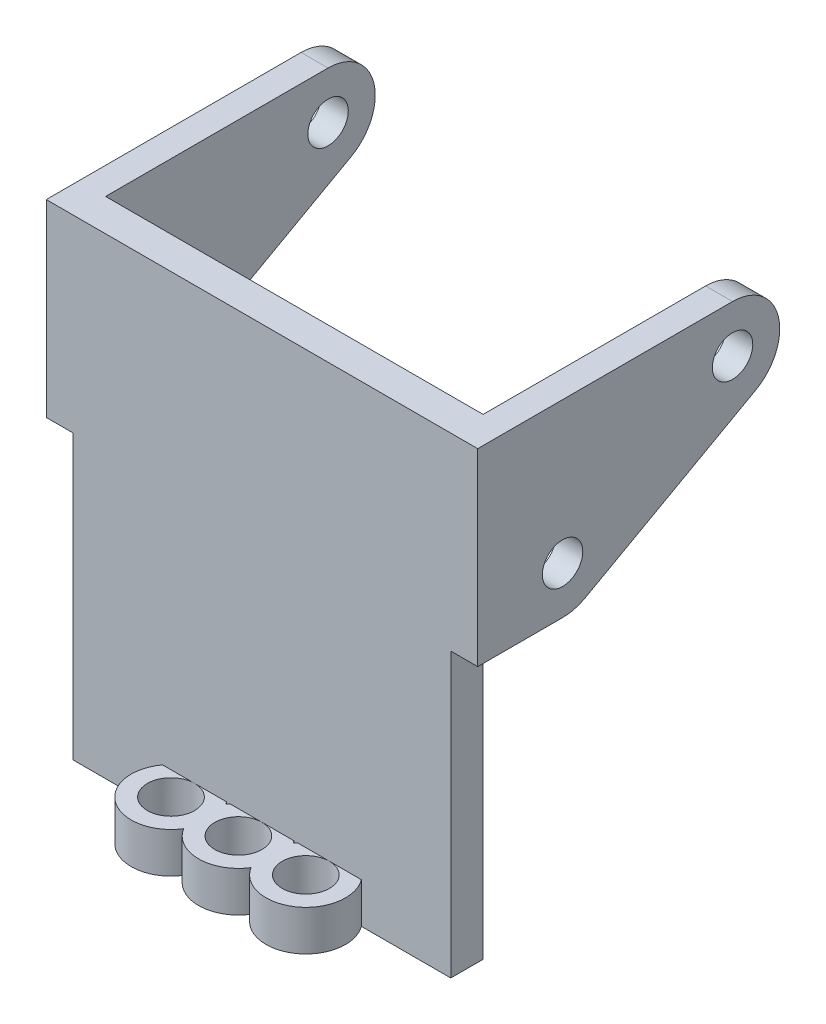
SolidWorks part; units mm, degrees
note: The reader was unsure of these and kept them because the rebuilt part matched: shared geometry of "Sketch4<2>".
ref_plane "Front Plane" through (0, 0, 0) normal (0, 0, 1) x (1, 0, 0)
ref_plane "Top Plane" through (0, 0, 0) normal (0, 1, 0) x (1, 0, 0)
ref_plane "Right Plane" through (0, 0, 0) normal (1, 0, 0) x (0, 0, -1)
sketch "Sketch2" plane through (0, 0, 0) normal (0, 1, 0) x (1, 0, 0)
  line L0 (-5, 0) -> (5, 0) construction
  circle A0 centre (0, 0) radius 1.75
  circle A1 centre (5, 0) radius 1.75
  circle A2 centre (-5, 0) radius 1.75
  dimension "D1" = 3.5
  dimension "D2" = 5
extrude "Extrude-Thin1" add sketch "Sketch2" along normal blind 3 thin contours A2 | A0 | A1
sketch "Sketch3" plane through (0, 0, 0) normal (1, 0, 0) x (0, 0, -1)
  line L0 (1.75, 0) -> (1.75, 35)
  line L1 (-2.95, 0) -> (2.95, 0) construction
  line L2 (4.15, 35) -> (54.15, 35) construction
extrude "Extrude-Thin2" add sketch "Sketch3" along normal up to surface (14 mm away) and the other way up to surface (14 mm away) thin
sketch "Sketch4" plane through (14, 0, 0) normal (1, 0, 0) x (0, 0, -1)
  line L0 (20.65, 35) -> (1.75, 35)
  line L1 (1.75, 35) -> (1.75, 21)
  line L2 (1.75, 0) -> (1.75, 35) construction
  line L3 (1.75, 21) -> (8.0415, 21)
  line L4 (9.7404, 21.44) -> (22.3489, 28.44)
  circle A0 centre (20.65, 31.5) radius 1.5 construction
  circle A1 centre (8.0415, 24.5) radius 1.5 construction
  circle A2 centre (20.65, 31.5) radius 1.5
  circle A3 centre (8.0415, 24.5) radius 1.5
  arc A4 (8.0415, 21) -> (9.7404, 21.44) centre (8.0415, 24.5) ccw
  arc A5 (22.3489, 28.44) -> (20.65, 35) centre (20.65, 31.5) ccw
  arc A7 (9.7404, 21.44) -> (8.0415, 21) centre (8.0415, 24.5) ccw construction
  circle A8 centre (8.0415, 24.5) radius 3.5 construction
  arc A9 (20.65, 35) -> (22.3489, 28.44) centre (20.65, 31.5) ccw construction
  circle A10 centre (20.65, 31.5) radius 3.5 construction
  point P7 (22.95, 31.5)
  point P12 (10.3415, 24.5)
extrude "Boss-Extrude1" add sketch "Sketch4" along normal blind 2
extrude "Boss-Extrude2" add sketch "Sketch4<2>" against normal blind 2 from surface at -28 starting at face at (-14, 17.5, -2.95)
sketch "Sketch4<2>" plane through (14, 0, 0) normal (1, 0, 0) x (0, 0, -1) same geometry as "Sketch4"
